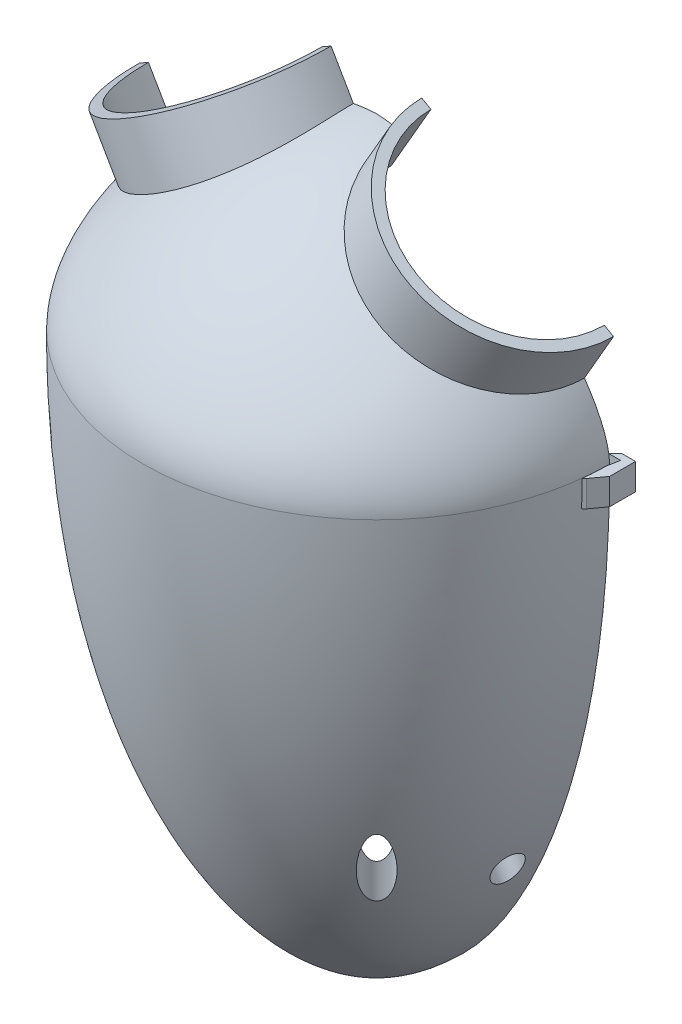
SolidWorks part; units mm, degrees
ref_plane "Front Plane" through (0, 0, 0) normal (0, 0, 1) x (1, 0, 0)
ref_plane "Top Plane" through (0, 0, 0) normal (0, 1, 0) x (1, 0, 0)
ref_plane "Right Plane" through (0, 0, 0) normal (1, 0, 0) x (0, 0, -1)
sketch "Sketch1" plane through (0, 0, 0) normal (0, 0, 1) x (1, 0, 0)
  line L4 (-0.0546, 35.5195) -> (-0.0546, 32.5195)
  line L8 (-0.0546, -99.6805) -> (-0.0546, -102.6805)
  line L10 (-0.0546, 0.0195) -> (34.9454, 0.0195) construction
  line L16 (-0.0546, 0.0195) -> (-0.0546, -93.3805) construction
  line L18 (34.9883, -22.2025) -> (34.9883, 22.1461) construction
  line L19 (36.2883, -22.6252) -> (36.9268, 22.5598) construction
  line L20 (49.2989, 26.1718) -> (-49.2989, 26.1718) construction
  line L21 (49.5414, 27.4718) -> (-49.5648, 27.4718) construction
  line L22 (-48.0253, -93.4282) -> (48.0253, -93.4282) construction
  line L23 (-50.9336, -99.6805) -> (50.8245, -99.6805) construction
  line L24 (36.6076, -190.5452) -> (36.6076, 190.4888) construction
  line L25 (34.9883, -187.8958) -> (34.9883, 187.8394) construction
  line L26 (-0.0546, 0.0195) -> (-0.0546, 26.2195) construction
  line L27 (-0.0546, 27.5195) -> (-0.0546, 26.2195) construction
  line L28 (34.9454, 0.0195) -> (36.2454, 0.0195) construction
  line L29 (-0.0546, -93.3805) -> (-0.0546, -94.6805) construction
  line L30 (34.9454, -22.1548) -> (34.9454, 22.1938) construction
  line L31 (36.2454, -22.5775) -> (36.2454, 22.6165) construction
  line L32 (49.2443, 26.2195) -> (-49.3535, 26.2195) construction
  line L33 (49.4985, 27.5195) -> (-49.6077, 27.5195) construction
  line L34 (-48.0798, -93.3805) -> (47.9707, -93.3805) construction
  line L35 (-50.9336, -94.6805) -> (50.8245, -94.6805) construction
  line L36 (36.2454, -190.4975) -> (36.2454, 190.5365) construction
  line L37 (34.9454, -187.8481) -> (34.9454, 187.8871) construction
  spline S0 degree 3 poles (44.2454, 0.0195) (44.2454, -67.7986) (17.9454, -102.6805) (-0.0546, -102.6805) knots 0 0 0 0 1 1 1 1
  spline S1 degree 3 poles (41.2454, 0.0195) (41.5779, -63.313) (18.6874, -99.5148) (-0.0546, -99.6805) knots 0 0 0 0 1 1 1 1
  spline S2 degree 3 poles (34.9454, 0.0195) (34.9454, -62.3138) (16.6121, -93.3805) (-0.0546, -93.3805) knots 0 0 0 0 1 1 1 1 construction
  spline S3 degree 3 poles (36.2454, 0.0195) (36.2454, -63.3138) (17.2787, -94.6805) (-0.0546, -94.6805) knots 0 0 0 0 1 1 1 1 construction
  spline S4 degree 3 poles (-0.0546, 27.5195) (16.9454, 27.5195) (36.2454, 7.6862) (36.2454, 0.0195) knots 0 0 0 0 1 1 1 1 construction
  spline S5 degree 3 poles (-0.0546, 26.2195) (16.6121, 26.2195) (34.9454, 7.3528) (34.9454, 0.0195) knots 0 0 0 0 1 1 1 1 construction
  spline S6 degree 3 poles (41.2454, 0.0195) (40.9583, 9.0149) (18.6069, 32.0799) (-0.0546, 32.5195) knots 0 0 0 0 1 1 1 1
  spline S7 degree 3 poles (44.2454, 0.0195) (43.8852, 12.3476) (21.9056, 34.1963) (-0.0546, 35.5195) knots 0 0 0 0 1 1 1 1
  point P0 (41.2454, 0.0195)
  point P44 (0, -94.7)
  dimension "D7" = 54
  dimension "D8" = 190
  dimension "D9" = 56
  dimension "D10" = 3
  dimension "D11" = 3
  dimension "D12" = 22
  dimension "D13" = 27
  dimension "D14" = 3
  dimension "D15" = 37
  dimension "D16" = 66
  dimension "D5" = 51
  dimension "D4" = 5
  dimension "D2" = 5
  dimension "D3" = 5
sketch "Sketch6" plane through (0, 0, 0) normal (0, 0, 1) x (1, 0, 0)
  line L0 (0, 0) -> (35, 0) construction
  line L1 (0, 0) -> (0, -93.4) construction
  line L2 (0, 0) -> (0, 26.2) construction
  line L3 (0, 27.5) -> (0, 26.2)
  line L4 (35, 0) -> (36.3, 0) construction
  line L5 (0, -93.4) -> (0, -94.7)
  line L6 (35, -22.1743) -> (35, 22.1743) construction
  line L7 (36.3, -22.597) -> (36.3, 22.597) construction
  line L8 (49.2989, 26.2) -> (-49.2989, 26.2) construction
  line L9 (49.5531, 27.5) -> (-49.5531, 27.5) construction
  line L10 (-48.0253, -93.4) -> (48.0253, -93.4) construction
  line L11 (-50.8791, -94.7) -> (50.8791, -94.7) construction
  line L12 (36.3, -190.517) -> (36.3, 190.517) construction
  line L13 (35, -187.8676) -> (35, 187.8676) construction
  spline S0 degree 3 poles (35, 0) (35, -62.3333) (16.6667, -93.4) (0, -93.4) knots 0 0 0 0 1 1 1 1
  spline S1 degree 3 poles (36.3, 0) (36.3, -63.3333) (17.3333, -94.7) (0, -94.7) knots 0 0 0 0 1 1 1 1
  spline S2 degree 3 poles (0, 27.5) (17, 27.5) (36.3, 7.6667) (36.3, 0) knots 0 0 0 0 1 1 1 1
  spline S3 degree 3 poles (0, 26.2) (16.6667, 26.2) (35, 7.3333) (35, 0) knots 0 0 0 0 1 1 1 1
  dimension "D7" = 90
  dimension "D8" = 90
  dimension "D9" = 23
  dimension "D10" = 22
  dimension "D11" = 90
  dimension "D12" = 90
  dimension "D13" = 50
  dimension "D14" = 51
  dimension "D15" = 90
  dimension "D16" = 90
  dimension "D17" = 50
  dimension "D18" = 52
  dimension "D19" = 90
  dimension "D20" = 90
  dimension "D21" = 190
  dimension "D22" = 187
  dimension "D1" = 1.3
  dimension "D2" = 93.4
  dimension "D3" = 35
  dimension "D4" = 1.3
  dimension "D5" = 1.3
  dimension "D6" = 26.2
revolve "Revolve1" add sketch "Sketch1" angle 360 about L16
ref_plane "Plane1" through (0, 30, 0) normal (0, 1, 0) x (1, 0, 0)
sketch "Sketch7" plane through (0, 30, 0) normal (0, 1, 0) x (1, 0, 0)
  line L0 (0, -42.4192) -> (0, 15.7817)
ref_plane "Plane2" through (-12.9904, 22.5, 0) normal (-0.5, 0.866, 0) x (0, 0, -1)
sketch "Sketch8" plane through (-12.9904, 22.5, 0) normal (-0.5, 0.866, 0) x (0, 0, -1)
  circle A0 centre (0, 7.3575) radius 19.025
  ellipse E1 centre (0, 0.0375) end of major axis (-44.3, 0.0375) minor radius 38.3649 construction
  dimension "D2" = 38.05
  dimension "D1" = 7.32
sketch "Sketch9" plane through (-12.9904, 22.5, 0) normal (-0.5, 0.866, 0) x (0, 0, -1)
  circle A0 centre (0, 7.3575) radius 21.025
  dimension "D2" = 42.05
ref_plane "Plane3" through (12.9904, 22.5, 0) normal (0.5, 0.866, 0) x (0, 0, -1)
sketch "Sketch10" plane through (12.9904, 22.5, 0) normal (0.5, 0.866, 0) x (0, 0, -1)
  line L0 (0, 0) -> (0, -46.7) construction
  circle A0 centre (0, -7.253) radius 19.025
  ellipse E0 centre (0, 0.057) end of major axis (44.3, 0.057) minor radius 38.3649 construction
  dimension "D2" = 38.05
  dimension "D1" = 7.31
sketch "Sketch11" plane through (12.9904, 22.5, 0) normal (0.5, 0.866, 0) x (0, 0, -1)
  circle A0 centre (0, -7.253) radius 21.025
  dimension "D2" = 42.05
extrude "Boss-Extrude1" add sketch "Sketch11" along normal blind 15 contours A0
extrude "Cut-Extrude1" cut sketch "Sketch10" along normal blind 15 and the other way blind 15 contours A0
extrude "Boss-Extrude2" add sketch "Sketch9" along normal blind 15 contours A0
extrude "Cut-Extrude2" cut sketch "Sketch8" against normal blind 15 and the other way blind 15 contours A0
sketch "Sketch12" plane through (0, 0, 0) normal (0, 0, 1) x (1, 0, 0)
  line L1 (-50.3642, 51.7707) -> (49.4298, 51.7707)
  line L2 (-50.3642, 51.7707) -> (-50.3642, -104.1442)
  line L3 (-50.3642, -104.1442) -> (49.4298, -104.1442)
  line L4 (49.4298, 51.7707) -> (49.4298, -104.1442)
extrude "Cut-Extrude4" cut sketch "Sketch12" against normal through all contours L1 L4 L3 L2
sketch "Sketch13" plane through (0, 0, 0) normal (0, 1, 0) x (1, 0, 0)
  line L4 (-46.2495, -2.0057) -> (-46.2495, 2.9119)
  line L10 (-44.3882, -4.5758) -> (-46.2495, -2.0057)
  line L12 (-46.2495, 2.9119) -> (-43.7314, 2.9119)
  line L13 (-43.7314, 2.9119) -> (-42.3823, 1.6666)
  line L14 (-44.6469, 1.6666) -> (-42.3823, 1.6666)
  line L15 (-44.6469, 1.6666) -> (-44.3546, 0)
  line L16 (-44.3546, 0) -> (-42.8761, -5.8916)
  line L17 (-42.8761, -5.8916) -> (-44.3882, -4.5758)
  line L18 (-45.0704, 0) -> (-43.3383, 0) construction
  point P3 (-46.2495, -2.0057)
  point P4 (-44.6154, 0)
  point P6 (-43.3383, 0)
  point P7 (-42.6414, -5.0931)
  point P16 (-44.3546, 0)
  point P18 (-44.3546, 1.6666)
  point P19 (-44.6469, 1.6666)
extrude "Boss-Extrude3" add sketch "Sketch13" against normal blind 5 contours L13 L14 L15 L16 L17 L10 L4 L12
sketch "Sketch14" plane through (0, 0, 0) normal (1, 0, 0) x (0, 0, -1)
  line L19 (-4.8279, -101.901) -> (0.0016, -102.0471)
  line L20 (0.0016, -102.0471) -> (4.0834, -102.0471)
  line L21 (4.0834, -102.0471) -> (4.0834, -99.1836)
  line L22 (4.0834, -99.1836) -> (2.0425, -97.1427)
  line L23 (2.0425, -97.1427) -> (2.0425, -99.1836)
  line L24 (2.0425, -99.1836) -> (0, -102.6805)
  line L25 (0, -102.6805) -> (-1.9145, -97.899)
  line L26 (-1.9145, -97.899) -> (-4.8279, -101.901)
  spline S0 degree 3 poles (-44.3, 0.0195) (-44.3, -67.7986) (-18, -102.6805) (0, -102.6805) knots 0 0 0 0 1 1 1 1 construction
mirror "Mirror1" about plane through (0, 0, 0) normal (1, 0, 0) of "Boss-Extrude3"
sketch "Sketch15" plane through (0, 0, 0) normal (0, 1, 0) x (1, 0, 0)
  circle A0 centre (-24.05, -24.05) radius 2.75
  point P2 (0, -34)
  point P3 (0, -31.3749)
  point P4 (-20.9079, -25.6563)
  dimension "D1" = 24.05
  dimension "D2" = 24.05
extrude "Cut-Extrude5" cut sketch "Sketch15" against normal through all
pattern_circular "CirPattern1" count 4 every 90 about axis through (-0.0546, 0.0195, 0) along (0, 1, 0) of "Cut-Extrude5"
sketch "Sketch16" plane through (-12.9904, 22.5, 0) normal (-0.5, 0.866, 0) x (0, 0, -1)
  circle A0 centre (-6.5, 7.6662) radius 2.75
sketch "Sketch18" plane through (12.9904, 22.5, 0) normal (0.5, 0.866, 0) x (0, 0, -1)
  circle A0 centre (-6.5, -7.6898) radius 2.75
  dimension "D3" = 5.5
  dimension "D1" = 21.4618
  dimension "D2" = 6.5
extrude "Cut-Extrude6" cut sketch "Sketch18" against normal blind 111 and the other way through all
extrude "Cut-Extrude7" cut sketch "Sketch16" against normal blind 111 contours A0
